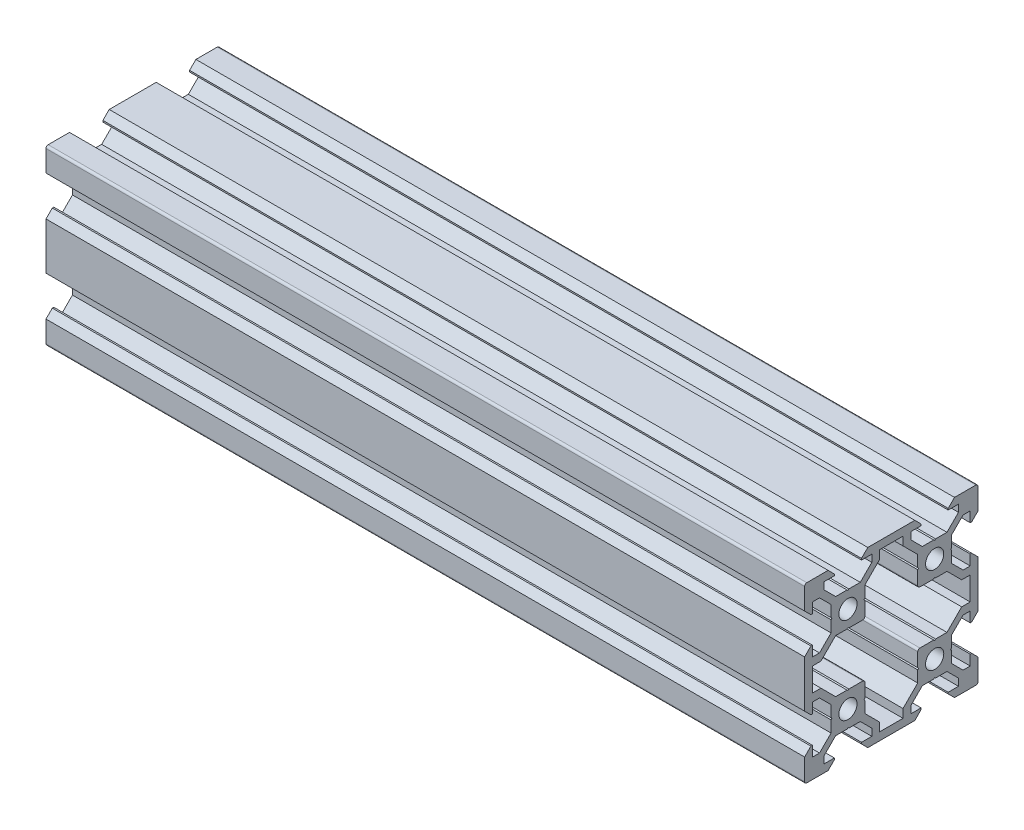
SolidWorks part; units mm, degrees
material "6061-T6 (SS)"
ref_plane "Top" through (0, 0, 0) normal (0, 0, 1) x (1, 0, 0)
ref_plane "Front" through (0, 0, 0) normal (0, 1, 0) x (1, 0, 0)
ref_plane "Right" through (0, 0, 0) normal (1, 0, 0) x (0, 0, -1)
sketch "Profile Sketch" plane through (0, 0, 0) normal (1, 0, 0) x (0, 0, -1)
  line L0 (0, 10) -> (-5.42, 10)
  line L1 (-4.5, 8.2) -> (-4.5, 6.56)
  line L2 (-4.5, 6.56) -> (-7.16, 3.9)
  line L3 (-7.16, 3.9) -> (-9.79, 3.9)
  line L4 (-9.79, 3.9) -> (-10, 3.69)
  line L5 (2.7, 8.2) -> (-2.7, 8.2)
  line L6 (-2.7, 8.2) -> (-2.7, 6.2387)
  line L7 (-2.7, 6.2387) -> (-6.1, 2.8387)
  line L8 (-6.1, 2.8387) -> (-6.1, 0.21)
  line L9 (-6.875, 8.545) -> (-6.875, 8.2)
  line L10 (-6.875, 8.2) -> (-4.5, 8.2)
  line L11 (-6.875, 8.545) -> (-5.42, 10)
  line L12 (0, -10) -> (0, 10) construction
  line L13 (-20, 0) -> (20, 0) construction
  line L14 (-10, -10) -> (-10, 10) construction
  line L21 (-6.6, -3.9) -> (-9.79, -3.9)
  line L25 (-10, 0) -> (-20, 10) construction
  line L26 (-18.545, 3.125) -> (-18.2, 3.125)
  line L31 (-16.2383, -7.3) -> (-12.84, -3.9)
  line L32 (-12.84, -3.9) -> (-10.21, -3.9)
  line L33 (-20, 4.58) -> (-20, 9.5)
  line L34 (-13.9, 2.8387) -> (-13.9, 0.21)
  line L35 (-16.56, 5.5) -> (-13.9, 2.8387)
  line L36 (-12.84, 3.9) -> (-10.21, 3.9)
  line L37 (-15.5, 6.56) -> (-12.84, 3.9)
  line L38 (-15.5, 8.2) -> (-15.5, 6.56)
  line L39 (-13.125, 8.545) -> (-14.58, 10)
  line L40 (-13.125, 8.2) -> (-15.5, 8.2)
  line L41 (-13.125, 8.545) -> (-13.125, 8.2)
  line L42 (-18.2, 3.125) -> (-18.2, 5.5)
  line L43 (-18.545, 3.125) -> (-20, 4.58)
  line L44 (-18.2, 5.5) -> (-16.56, 5.5)
  line L45 (-14.58, 10) -> (-19.5, 10)
  line L46 (-16.56, -5.5) -> (-13.9, -2.8387)
  line L48 (-18.2, -5.5) -> (-16.56, -5.5)
  line L49 (-18.545, -3.125) -> (-20, -4.58)
  line L50 (-18.2, -3.125) -> (-18.2, -5.5)
  line L51 (-20, -4.58) -> (-20, -15.42)
  line L52 (-18.545, -3.125) -> (-18.2, -3.125)
  line L53 (9.79, -3.9) -> (10, -3.69)
  line L99 (-10, 3.69) -> (-10.21, 3.9)
  line L100 (-10, -3.69) -> (-10.21, -3.9)
  line L101 (-9.79, -3.9) -> (-10, -3.69)
  line L102 (-13.9, -0.21) -> (-13.69, 0)
  line L103 (-13.69, 0) -> (-13.9, 0.21)
  line L104 (-13.9, -0.21) -> (-13.9, -2.8387)
  line L105 (-6.1, -0.21) -> (-6.31, 0)
  line L106 (-6.31, 0) -> (-6.1, -0.21)
  line L107 (-6.1, -0.21) -> (-6.1, -3.4)
  line L117 (-16.2383, -7.3) -> (-18.2, -7.3)
  line L118 (20, -10) -> (20, 10) construction
  line L119 (20, -10) -> (-20, -10) construction
  line L120 (-20, -10) -> (-20, 10) construction
  line L121 (20, 10) -> (-20, 10) construction
  line L122 (6.6, -3.9) -> (9.79, -3.9)
  line L123 (10, -3.69) -> (10.21, -3.9)
  line L124 (-18.2, -7.3) -> (-18.2, -12.7)
  line L125 (12.84, -3.9) -> (10.21, -3.9)
  line L126 (-6.31, 0) -> (-6.1, 0.21)
  line L127 (16.2383, -7.3) -> (12.84, -3.9)
  line L128 (20, -4.58) -> (20, -15.42)
  line L129 (18.2, -7.3) -> (18.2, -12.7)
  line L130 (16.2383, -7.3) -> (18.2, -7.3)
  line L131 (18.545, -3.125) -> (18.2, -3.125)
  line L132 (18.2, -3.125) -> (18.2, -5.5)
  line L133 (18.545, -3.125) -> (20, -4.58)
  line L134 (18.2, -5.5) -> (16.56, -5.5)
  line L135 (16.56, -5.5) -> (13.9, -2.8387)
  line L136 (13.9, -0.21) -> (13.9, -2.8387)
  line L137 (13.69, 0) -> (13.9, 0.21)
  line L138 (13.9, -0.21) -> (13.69, 0)
  line L139 (13.9, 2.8387) -> (13.9, 0.21)
  line L140 (18.2, 5.5) -> (16.56, 5.5)
  line L141 (18.545, 3.125) -> (20, 4.58)
  line L142 (18.2, 3.125) -> (18.2, 5.5)
  line L143 (16.56, 5.5) -> (13.9, 2.8387)
  line L144 (18.545, 3.125) -> (18.2, 3.125)
  line L145 (20, 4.58) -> (20, 9.5)
  line L146 (14.58, 10) -> (19.5, 10)
  line L147 (13.125, 8.545) -> (13.125, 8.2)
  line L148 (13.125, 8.2) -> (15.5, 8.2)
  line L149 (13.125, 8.545) -> (14.58, 10)
  line L150 (15.5, 8.2) -> (15.5, 6.56)
  line L151 (15.5, 6.56) -> (12.84, 3.9)
  line L152 (12.84, 3.9) -> (10.21, 3.9)
  line L153 (10, 3.69) -> (10.21, 3.9)
  line L154 (9.79, 3.9) -> (10, 3.69)
  line L155 (6.1, -0.21) -> (6.1, -3.4)
  line L156 (6.1, -0.21) -> (6.31, 0)
  line L157 (6.31, 0) -> (6.1, 0.21)
  line L158 (6.1, 2.8387) -> (6.1, 0.21)
  line L159 (7.16, 3.9) -> (9.79, 3.9)
  line L160 (2.7, 6.2387) -> (6.1, 2.8387)
  line L161 (4.5, 6.56) -> (7.16, 3.9)
  line L162 (6.875, 8.545) -> (6.875, 8.2)
  line L163 (6.875, 8.2) -> (4.5, 8.2)
  line L164 (4.5, 8.2) -> (4.5, 6.56)
  line L165 (2.7, 8.2) -> (2.7, 6.2387)
  line L166 (6.875, 8.545) -> (5.42, 10)
  line L167 (0, 10) -> (5.42, 10)
  line L168 (-20, -24.58) -> (-20, -29.5)
  line L169 (-14.58, -30) -> (-19.5, -30)
  line L170 (-7.16, -23.9) -> (-9.79, -23.9)
  line L171 (-10, -23.69) -> (-10.21, -23.9)
  line L172 (-9.79, -23.9) -> (-10, -23.69)
  line L173 (-12.84, -23.9) -> (-10.21, -23.9)
  line L174 (-13.125, -28.545) -> (-13.125, -28.2)
  line L175 (-13.125, -28.2) -> (-15.5, -28.2)
  line L176 (-13.125, -28.545) -> (-14.58, -30)
  line L177 (-15.5, -28.2) -> (-15.5, -26.56)
  line L178 (-15.5, -26.56) -> (-12.84, -23.9)
  line L179 (-18.2, -25.5) -> (-16.56, -25.5)
  line L180 (-18.545, -23.125) -> (-20, -24.58)
  line L181 (-18.2, -23.125) -> (-18.2, -25.5)
  line L182 (-16.56, -25.5) -> (-13.9, -22.8387)
  line L183 (-18.545, -23.125) -> (-18.2, -23.125)
  line L184 (-13.9, -19.79) -> (-13.9, -17.1613)
  line L185 (-13.69, -20) -> (-13.9, -20.21)
  line L186 (-13.9, -19.79) -> (-13.69, -20)
  line L187 (-13.9, -22.8387) -> (-13.9, -20.21)
  line L188 (-16.2383, -12.7) -> (-18.2, -12.7)
  line L189 (-18.545, -16.875) -> (-18.2, -16.875)
  line L190 (-18.2, -16.875) -> (-18.2, -14.5)
  line L191 (-18.545, -16.875) -> (-20, -15.42)
  line L192 (-18.2, -14.5) -> (-16.56, -14.5)
  line L193 (-16.56, -14.5) -> (-13.9, -17.1613)
  line L194 (-16.2383, -12.7) -> (-12.84, -16.1)
  line L195 (-9.79, -16.1) -> (-10, -16.31)
  line L196 (-10, -16.31) -> (-10.21, -16.1)
  line L197 (-12.84, -16.1) -> (-10.21, -16.1)
  line L198 (-6.6, -16.1) -> (-9.79, -16.1)
  line L199 (-6.1, -19.79) -> (-6.1, -16.6)
  line L200 (-6.1, -22.8387) -> (-6.1, -20.21)
  line L201 (-6.31, -20) -> (-6.1, -20.21)
  line L202 (-6.31, -20) -> (-6.1, -19.79)
  line L203 (-6.1, -19.79) -> (-6.31, -20)
  line L204 (-2.7, -26.2387) -> (-6.1, -22.8387)
  line L205 (-4.5, -26.56) -> (-7.16, -23.9)
  line L206 (-4.5, -28.2) -> (-4.5, -26.56)
  line L207 (-6.875, -28.2) -> (-4.5, -28.2)
  line L208 (-6.875, -28.545) -> (-6.875, -28.2)
  line L209 (-6.875, -28.545) -> (-5.42, -30)
  line L210 (0, -30) -> (-5.42, -30)
  line L211 (0, -30) -> (5.42, -30)
  line L212 (14.58, -30) -> (19.5, -30)
  line L213 (20, -24.58) -> (20, -29.5)
  line L214 (6.875, -28.545) -> (5.42, -30)
  line L215 (2.7, -28.2) -> (2.7, -26.2387)
  line L216 (4.5, -28.2) -> (4.5, -26.56)
  line L217 (6.875, -28.2) -> (4.5, -28.2)
  line L218 (6.875, -28.545) -> (6.875, -28.2)
  line L219 (4.5, -26.56) -> (7.16, -23.9)
  line L220 (2.7, -26.2387) -> (6.1, -22.8387)
  line L221 (7.16, -23.9) -> (9.79, -23.9)
  line L222 (6.1, -22.8387) -> (6.1, -20.21)
  line L223 (9.79, -23.9) -> (10, -23.69)
  line L224 (10, -23.69) -> (10.21, -23.9)
  line L225 (12.84, -23.9) -> (10.21, -23.9)
  line L226 (15.5, -26.56) -> (12.84, -23.9)
  line L227 (15.5, -28.2) -> (15.5, -26.56)
  line L228 (13.125, -28.545) -> (14.58, -30)
  line L229 (13.125, -28.2) -> (15.5, -28.2)
  line L230 (13.125, -28.545) -> (13.125, -28.2)
  line L231 (18.545, -23.125) -> (18.2, -23.125)
  line L232 (16.56, -25.5) -> (13.9, -22.8387)
  line L233 (18.2, -23.125) -> (18.2, -25.5)
  line L234 (18.545, -23.125) -> (20, -24.58)
  line L235 (18.2, -25.5) -> (16.56, -25.5)
  line L236 (13.9, -22.8387) -> (13.9, -20.21)
  line L237 (2.7, -28.2) -> (-2.7, -28.2)
  line L238 (6.31, -20) -> (6.1, -20.21)
  line L239 (6.1, -19.79) -> (6.31, -20)
  line L240 (13.9, -19.79) -> (13.69, -20)
  line L241 (13.69, -20) -> (13.9, -20.21)
  line L242 (6.1, -19.79) -> (6.1, -16.6)
  line L243 (13.9, -19.79) -> (13.9, -17.1613)
  line L244 (16.56, -14.5) -> (13.9, -17.1613)
  line L245 (18.2, -14.5) -> (16.56, -14.5)
  line L246 (18.545, -16.875) -> (20, -15.42)
  line L247 (18.2, -16.875) -> (18.2, -14.5)
  line L248 (18.545, -16.875) -> (18.2, -16.875)
  line L249 (16.2383, -12.7) -> (18.2, -12.7)
  line L250 (16.2383, -12.7) -> (12.84, -16.1)
  line L251 (12.84, -16.1) -> (10.21, -16.1)
  line L252 (10, -16.31) -> (10.21, -16.1)
  line L253 (6.6, -16.1) -> (9.79, -16.1)
  line L254 (9.79, -16.1) -> (10, -16.31)
  line L255 (-2.7, -26.2387) -> (-2.7, -28.2)
  circle A0 centre (-10, 0) radius 2.1
  arc A1 (-19.5, 10) -> (-20, 9.5) centre (-19.5, 9.5) ccw
  arc A2 (-6.6, -3.9) -> (-6.1, -3.4) centre (-6.6, -3.4) ccw
  arc A3 (6.6, -3.9) -> (6.1, -3.4) centre (6.6, -3.4) cw
  circle A4 centre (10, 0) radius 2.1
  arc A5 (19.5, 10) -> (20, 9.5) centre (19.5, 9.5) cw
  arc A6 (-19.5, -30) -> (-20, -29.5) centre (-19.5, -29.5) cw
  arc A7 (-6.6, -16.1) -> (-6.1, -16.6) centre (-6.6, -16.6) cw
  arc A8 (19.5, -30) -> (20, -29.5) centre (19.5, -29.5) ccw
  circle A9 centre (10, -20) radius 2.1
  arc A10 (6.6, -16.1) -> (6.1, -16.6) centre (6.6, -16.6) ccw
  circle A11 centre (-10, -20) radius 2.1
  point P35 (-2.4957, 0)
  point P119 (0, 18.9743)
  point P121 (0, 8.2)
  point P123 (2.4957, 0)
  point P131 (0, 0)
  point P143 (0, 0)
  point P164 (-18.2, -10)
  point P234 (18.2, -10)
  dimension "D4" = 5.42
  dimension "D5" = 40
  dimension "D6" = 4.2
  dimension "D16" = 0.5
  dimension "D17" = 0.5
  dimension "D2" = 45
  dimension "D3" = 20
  dimension "D7" = 1.5
  dimension "D9" = 10
  dimension "D10" = 3.9
  dimension "D11" = 3.9
  dimension "D13" = 3.125
  dimension "D14" = 5.5
  dimension "D15" = 1.64
  dimension "Knotch Depth" = 0.21
extrude "Profile Extrude" add sketch "Profile Sketch" along normal blind 175 contours L0 L11 L9 L10 L1 L2 L3 L4 L99 L36 L37 L38 L40 L41 L39 L45 A1 L33 L43 L26 L42 L44 L35 L34 L103 L102 L104 L46 L48 L50 L52 L49 L51 region at (0, 9.4343, -2.71)
